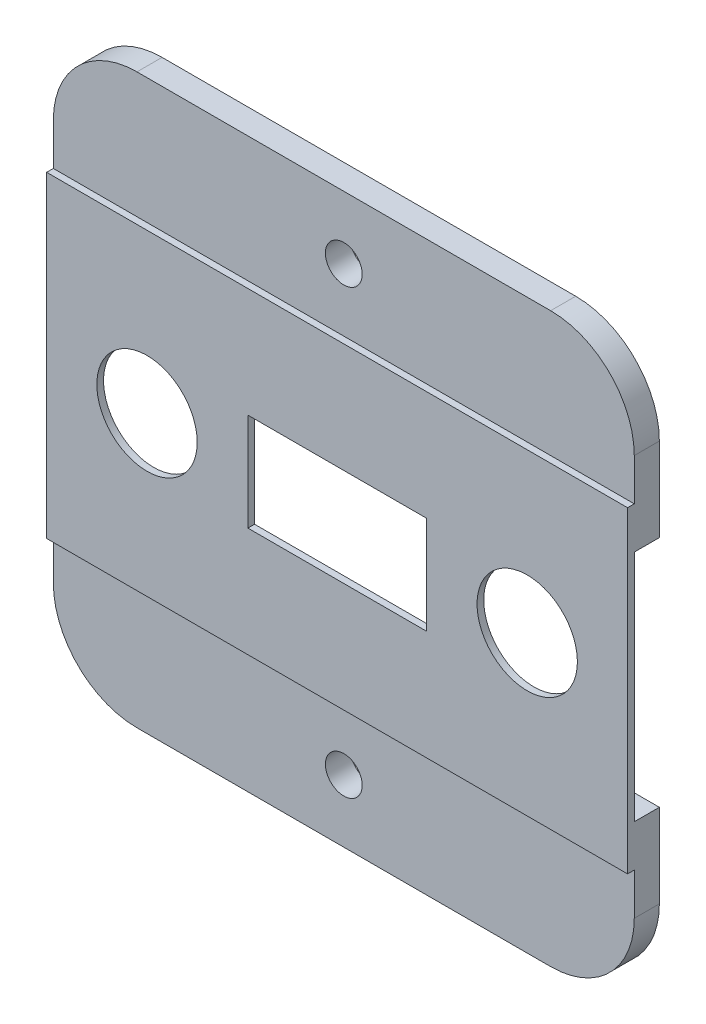
SolidWorks part; units mm, degrees
ref_plane "Front Plane" through (0, 0, 0) normal (0, 0, 1) x (1, 0, 0)
ref_plane "Top Plane" through (0, 0, 0) normal (0, 1, 0) x (1, 0, 0)
ref_plane "Right Plane" through (0, 0, 0) normal (1, 0, 0) x (0, 0, -1)
sketch "Sketch1" plane through (0, 0, 0) normal (0, 0, 1) x (1, 0, 0)
  line L1 (-21.2854, -18.6229) -> (-21.2854, -12.2729)
  line L2 (-14.9354, -5.9229) -> (16.4717, -5.9229)
  line L51 (-8.6743, -18.6229) -> (22.1091, -18.6229)
  line L52 (-21.2854, -18.6229) -> (22.8217, -18.6229) construction
  line L54 (-8.6743, -36.3521) -> (22.1091, -36.3521)
  line L55 (-21.2854, -36.3521) -> (22.8217, -36.3521) construction
  line L56 (-21.2854, -36.3521) -> (22.8217, -36.3521)
  line L57 (-21.2854, -36.3521) -> (-21.2854, -42.7021)
  line L58 (-14.9354, -49.0521) -> (16.4717, -49.0521)
  line L59 (22.8217, -36.3521) -> (22.8217, -42.7021)
  line L60 (22.8217, -18.6229) -> (-21.2854, -18.6229)
  line L61 (22.8217, -18.6229) -> (22.8217, -12.2729)
  circle A0 centre (-13.6654, -27.4875) radius 1.319 construction
  circle A1 centre (15.2017, -27.4875) radius 1.319 construction
  circle A2 centre (-13.6654, -27.4875) radius 1.319 construction
  circle A3 centre (15.2017, -27.4875) radius 1.319 construction
  arc A8 (-14.9354, -49.0521) -> (-21.2854, -42.7021) centre (-14.9354, -42.7021) cw
  arc A9 (16.4717, -49.0521) -> (22.8217, -42.7021) centre (16.4717, -42.7021) ccw
  arc A10 (16.4717, -5.9229) -> (22.8217, -12.2729) centre (16.4717, -12.2729) cw
  arc A11 (-21.2854, -12.2729) -> (-14.9354, -5.9229) centre (-14.9354, -12.2729) cw
  point P3 (-21.2854, -49.0521)
  point P21 (-21.2854, -49.0521)
  dimension "D6" = 7.62
  dimension "D4" = 6.35
  dimension "D3" = 12.7
  dimension "D5" = 7.62
  dimension "D1" = 0.508
  dimension "D2" = 0.508
extrude "Boss-Extrude1" add sketch "Sketch1" along normal offset from surface (1.905 mm away) 0.381 contours L60 L1 A11 L2 A10 L61 | L58 A9 L59 L56 L57 A8 offset beyond the face yes
sketch "Sketch2" plane through (0, 0, 1.905) normal (0, 0, 1) x (1, 0, 0)
  line L0 (-5.2453, -30.2624) -> (-5.2453, -30.4402) construction
  line L1 (-21.2854, -39.5271) -> (22.8217, -39.5271)
  line L7 (22.8217, -15.4479) -> (-21.2854, -15.4479)
  line L9 (-5.2453, -30.2624) -> (-5.2453, -24.7125) construction
  line L10 (-5.2453, -24.5347) -> (-5.2453, -24.7125) construction
  line L11 (6.7816, -24.5347) -> (-5.2453, -24.5347) construction
  line L12 (6.7816, -30.4402) -> (6.7816, -24.5347) construction
  line L13 (-5.2453, -30.4402) -> (6.7816, -30.4402) construction
  line L14 (-5.2453, -30.2624) -> (-5.2453, -30.4402) construction
  line L15 (-5.2453, -30.2624) -> (-5.2453, -24.7125) construction
  line L16 (-5.2453, -24.5347) -> (-5.2453, -24.7125) construction
  line L17 (6.7816, -24.5347) -> (-5.2453, -24.5347) construction
  line L18 (6.7816, -30.4402) -> (6.7816, -24.5347) construction
  line L19 (-5.2453, -30.4402) -> (6.7816, -30.4402) construction
  line L20 (-6.0073, -23.7727) -> (-6.0073, -24.7125)
  line L21 (-6.0073, -30.2624) -> (-6.0073, -24.7125)
  line L26 (-6.0073, -30.2624) -> (-6.0073, -31.2022)
  line L27 (-6.0073, -31.2022) -> (7.5436, -31.2022)
  line L30 (7.5436, -31.2022) -> (7.5436, -23.7727)
  line L31 (7.5436, -23.7727) -> (-6.0073, -23.7727)
  line L32 (22.8217, -18.6229) -> (-21.2854, -18.6229) construction
  line L33 (-21.2854, -15.4479) -> (-21.2854, -39.5271)
  line L35 (22.8217, -39.5271) -> (22.8217, -15.4479)
  circle A0 centre (-13.6654, -27.4875) radius 1.397 construction
  circle A1 centre (15.2017, -27.4875) radius 1.397 construction
  circle A2 centre (-13.6654, -27.4875) radius 1.397 construction
  circle A3 centre (15.2017, -27.4875) radius 1.397 construction
  circle A4 centre (15.2017, -27.4875) radius 3.81
  circle A5 centre (-13.6654, -27.4875) radius 3.81
  arc A10 (10.2614, -23.6775) -> (10.2614, -31.2975) centre (10.2614, -27.4875) ccw construction
  point P37 (-5.2453, -27.4875)
  point P45 (-21.2854, -27.4875)
  dimension "D3" = 0.762
  dimension "D5" = 7.62
  dimension "D1" = 7.62
  dimension "D4" = 3.175
extrude "Boss-Extrude2" add sketch "Sketch2" along normal blind 0.508
sketch "Sketch3" plane through (0, 0, 1.905) normal (0, 0, 1) x (1, 0, 0)
  line L0 (22.8217, -15.4479) -> (-21.2854, -15.4479) construction
  line L1 (-21.2854, -39.5271) -> (22.8217, -39.5271) construction
  line L2 (-14.9354, -49.0521) -> (16.4717, -49.0521) construction
  line L3 (-14.9354, -5.9229) -> (16.4717, -5.9229) construction
  line L4 (22.8217, -15.4479) -> (-21.2854, -15.4479) construction
  line L5 (-21.2854, -39.5271) -> (22.8217, -39.5271) construction
  line L6 (-14.9354, -49.0521) -> (16.4717, -49.0521) construction
  line L7 (-14.9354, -5.9229) -> (16.4717, -5.9229) construction
  line L8 (0.7682, -5.9229) -> (0.7682, -15.4479) construction
  line L9 (0.7682, -39.5271) -> (0.7682, -49.0521) construction
  point P12 (0.7682, -44.2896)
  point P13 (0.7682, -10.6854)
  point P14 (0.7682, -10.6854)
hole_wizard "#3 Clearance Hole1" positions "Sketch6" profile "Sketch7" hole size "#3" standard "ANSI Inch" end condition through all
sketch "Sketch6" plane through (0, 0, 1.905) normal (0, 0, 1) x (1, 0, 0)
  point P0 (0.7682, -10.6854)
  point P3 (0.7682, -44.2896)
sketch "Sketch7" plane through (0.7682, -10.6854, 1.905) normal (1, 0, 0) x (0, -1, 0)
  line L0 (0, 0) -> (0, 1.905)
  line L1 (0, 1.905) -> (1.397, 1.905)
  line L2 (1.397, 1.905) -> (1.397, 0)
  line L5 (1.397, 0) -> (0, 0)
  line L11 (0, -6.35) -> (0, 107.95) construction
  dimension "Thru Hole Dia." = 2.794
  dimension "Thru Hole Depth" = 1.905
